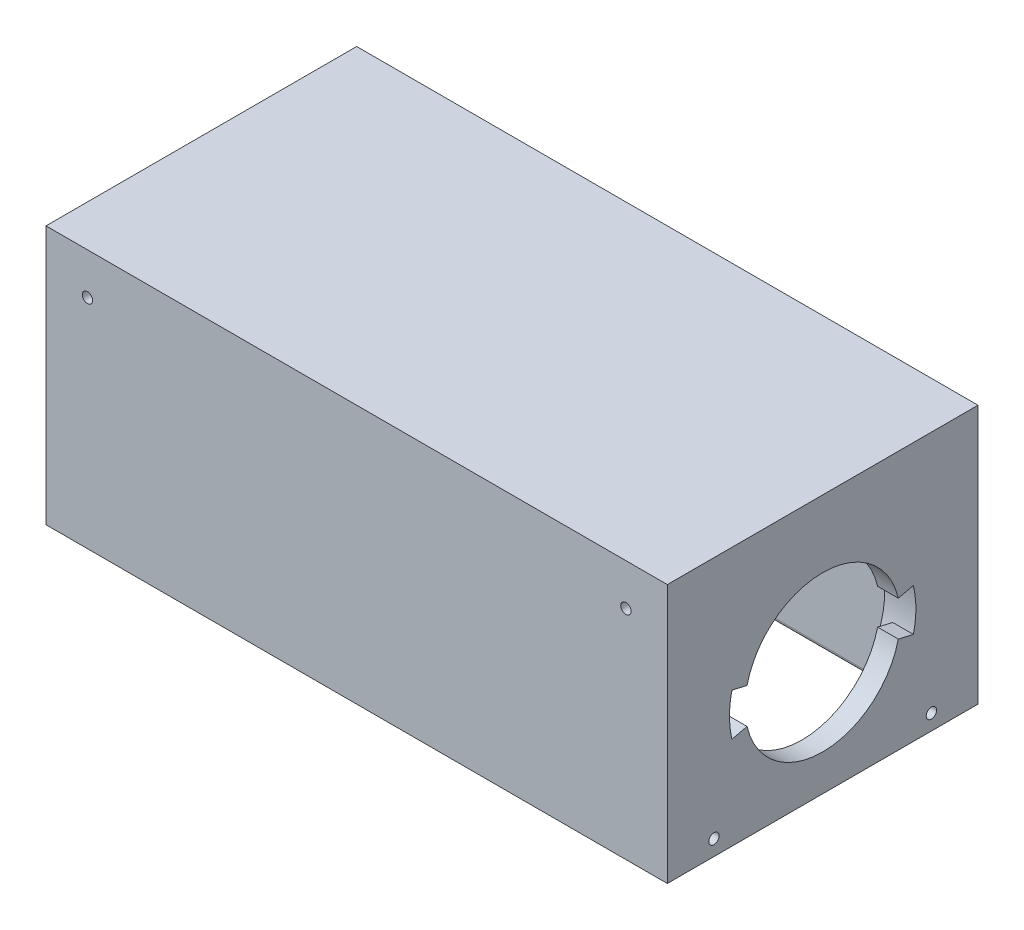
SolidWorks part; units mm, degrees
material "ABS PC"
ref_plane "Front Plane" through (0, 0, 0) normal (0, 0, 1) x (1, 0, 0)
ref_plane "Top Plane" through (0, 0, 0) normal (0, 1, 0) x (1, 0, 0)
ref_plane "Right Plane" through (0, 0, 0) normal (1, 0, 0) x (0, 0, -1)
sketch "Sketch1" plane through (0, 0, 0) normal (0, 1, 0) x (1, 0, 0)
  line L1 (150, -75) -> (-150, -75)
  line L2 (150, -75) -> (150, 75)
  line L3 (150, 75) -> (-150, 75)
  line L4 (-150, -75) -> (-150, 75)
  line L5 (150, -75) -> (-150, 75) construction
  line L6 (150, 75) -> (-150, -75) construction
  point P0 (0, 0)
  dimension "D1" = 300
  dimension "D2" = 150
extrude "Boss-Extrude1" add sketch "Sketch1" along normal blind 125
sketch "Sketch2" plane through (0, 0, 0) normal (0, -1, 0) x (1, 0, 0)
  line L0 (-150, 75) -> (150, 75) construction
  line L1 (135, -60) -> (-135, -60)
  line L2 (135, -60) -> (135, 60)
  line L3 (135, 60) -> (-135, 60)
  line L4 (-135, -60) -> (-135, 60)
  line L5 (135, -60) -> (-135, 60) construction
  line L6 (135, 60) -> (-135, -60) construction
  line L7 (150, 75) -> (150, -75) construction
  point P0 (0, 0)
  point P8 (150, 0)
  dimension "D1" = 15
  dimension "D2" = 15
extrude "Cut-Extrude1" cut sketch "Sketch2" against normal blind 110
sketch "Sketch4" plane through (150, 0, 0) normal (1, 0, 0) x (0, 0, -1)
  line L0 (-75, 0) -> (75, 0) construction
  line L1 (75, 125) -> (75, 0) construction
  line L5 (-75, 125) -> (-75, 0) construction
  circle A0 centre (-52.5, 7.5) radius 2.5
  circle A1 centre (52.5, 7.5) radius 2.5
  dimension "D3" = 5
  dimension "D4" = 5
  dimension "D1" = 7.5
  dimension "D2" = 22.5
  dimension "D5" = 7.5
  dimension "D6" = 22.5
extrude "Cut-Extrude5" cut sketch "Sketch4" against normal blind 350
sketch "Sketch6" plane through (0, 0, 75) normal (0, 0, 1) x (1, 0, 0)
  line L0 (-150, 125) -> (-150, 0) construction
  line L1 (-150, 125) -> (150, 125) construction
  line L2 (0, 140.9499) -> (0, -14.4188) construction
  circle A0 centre (-130, 105) radius 2.5
  circle A1 centre (130, 105) radius 2.5
  dimension "D1" = 5
  dimension "D2" = 20
  dimension "D3" = 20
extrude "Cut-Extrude6" cut sketch "Sketch6" against normal blind 175
fillet "Fillet1" radius 5 1 edges at (0, 110, -60)
fillet "Fillet2" radius 5 1 edges at (0, 110, 60)
fillet "Fillet3" radius 5 5 edges at (-135, 52.5, 60) (-135, 108.5355, 58.5355) (-135, 52.5, -60) (-135, 108.5355, -58.5355) (-135, 110, 0)
fillet "Fillet4" radius 5 5 edges at (135, 52.5, -60) (135, 108.5355, -58.5355) (135, 52.5, 60) (135, 108.5355, 58.5355) (135, 110, 0)
fillet "Fillet5" radius 2 8 edges at (-133.5355, 0, -58.5355) (-135, 0, 0) (-133.5355, 0, 58.5355) (0, 0, 60) (133.5355, 0, 58.5355) (135, 0, 0) (133.5355, 0, -58.5355) (0, 0, -60)
sketch "Sketch7" plane through (150, 0, 0) normal (1, 0, 0) x (0, 0, -1)
  line L0 (-75, 0) -> (75, 0) construction
  circle A0 centre (0, 55) radius 37.5
  dimension "D1" = 75
  dimension "D2" = 55
extrude "Cut-Extrude7" cut sketch "Sketch7" against normal blind 25
sketch "Sketch8" plane through (135, 0, 0) normal (-1, 0, 0) x (0, 0, 1)
  circle A0 centre (0, 55) radius 45
  dimension "D1" = 90
extrude "Cut-Extrude8" cut sketch "Sketch8" against normal blind 5
sketch "Sketch9" plane through (150, 0, 0) normal (1, 0, 0) x (0, 0, -1)
  line L0 (0, 141.2164) -> (0, -8.4534) construction
  line L1 (0, 55) -> (43.8171, 65.25)
  line L2 (43.8171, 44.75) -> (0, 55)
  line L3 (0, 55) -> (-43.8171, 65.25)
  line L4 (-43.8171, 44.75) -> (0, 55)
  arc A0 (43.8171, 65.25) -> (43.8171, 44.75) centre (0, 55) cw
  circle A1 centre (0, 55) radius 45 construction
  arc A2 (-43.8171, 65.25) -> (-43.8171, 44.75) centre (0, 55) ccw
  circle M3 centre (0, 55) radius 37.5
  dimension "D1" = 10.25
  dimension "D2" = 10.25
extrude "Cut-Extrude9" cut sketch "Sketch9" against normal blind 20 contours L3 A2 L4 M3 | A0 L1 L2 M3 region at (150, 55, -41.0006) region at (150, 55, 41.0006)
sketch "Sketch10" plane through (140, 0, 0) normal (-1, 0, 0) x (0, 0, 1)
  line L0 (-3.5, 99.8637) -> (-3.5, 92.3363)
  line L1 (3.5, 92.3363) -> (3.5, 99.8637)
  arc A0 (3.5, 99.8637) -> (-3.5, 99.8637) centre (0, 55) ccw
  circle A1 centre (0, 55) radius 45 construction
  arc A2 (3.5, 92.3363) -> (-3.5, 92.3363) centre (0, 55) ccw
  arc A3 (36.5142, 63.5417) -> (-36.5142, 63.5417) centre (0, 55) ccw construction
  dimension "D1" = 3.5
  dimension "D2" = 3.5
  dimension "D3" = 3.5
  dimension "D4" = 3.5
extrude "Boss-Extrude2" add sketch "Sketch10" along normal blind 5
sketch "Sketch12" plane through (0, 0, 0) normal (0, -1, 0) x (1, 0, 0)
  line L0 (150, 75) -> (150, -75) construction
  line L1 (-150, 75) -> (150, 75) construction
  line L2 (0, 0) -> (50000, 0) construction
  line L3 (0, 0) -> (0, -50000) construction
  circle A0 centre (144.7549, 69.7549) radius 2.0701
  circle A1 centre (144.7549, 69.7549) radius 5.2451 construction
  circle A2 centre (144.7549, -69.7549) radius 2.0701
  circle A3 centre (144.7549, -69.7549) radius 5.2451 construction
  circle A4 centre (-144.7549, -69.7549) radius 2.0701
  circle A5 centre (-144.7549, -69.7549) radius 5.2451 construction
  circle A6 centre (-144.7549, 69.7549) radius 2.0701
  circle A7 centre (-144.7549, 69.7549) radius 5.2451 construction
  dimension "D1" = 4.1402
  dimension "D2" = 3.175
extrude "Cut-Extrude10" cut sketch "Sketch12" against normal blind 12.7
